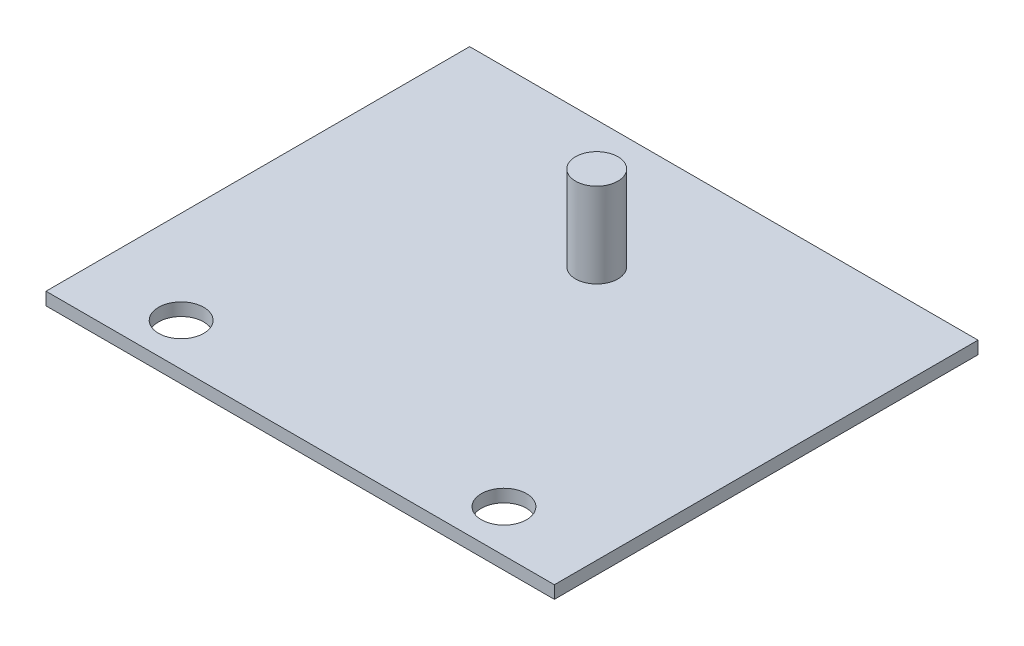
SolidWorks part; units mm, degrees
ref_plane "Front Plane" through (0, 0, 0) normal (0, 0, 1) x (1, 0, 0)
ref_plane "Top Plane" through (0, 0, 0) normal (0, 1, 0) x (1, 0, 0)
ref_plane "Right Plane" through (0, 0, 0) normal (1, 0, 0) x (0, 0, -1)
sketch "Sketch1" plane through (0, 0, 0) normal (0, 1, 0) x (1, 0, 0)
  line L1 (0, 0) -> (120, 0)
  line L2 (0, 0) -> (0, 100)
  line L3 (0, 100) -> (120, 100)
  line L4 (120, 0) -> (120, 100)
  dimension "D1" = 100
  dimension "D2" = 120
extrude "Boss-Extrude1" add sketch "Sketch1" along normal blind 3
sketch "Sketch2" plane through (0, 3, 0) normal (0, 1, 0) x (1, 0, 0)
  line L0 (60, 100) -> (60, 0) construction
  line L1 (120, 100) -> (0, 100) construction
  line L2 (0, 0) -> (120, 0) construction
  circle A0 centre (21.9, 10) radius 5.334
  circle A1 centre (98.1, 10) radius 5.334
  dimension "D1" = 10.668
  dimension "D2" = 76.2
  dimension "D3" = 10
extrude "Cut-Extrude1" cut sketch "Sketch2" against normal through all
sketch "Sketch3" plane through (0, 3, 0) normal (0, 1, 0) x (1, 0, 0)
  line L0 (60, 100) -> (60, 0) construction
  line L1 (120, 100) -> (0, 100) construction
  line L2 (0, 0) -> (120, 0) construction
  circle A0 centre (60, 70) radius 5
  dimension "D2" = 10
  dimension "D1" = 30
extrude "Boss-Extrude2" add sketch "Sketch3" along normal blind 20
